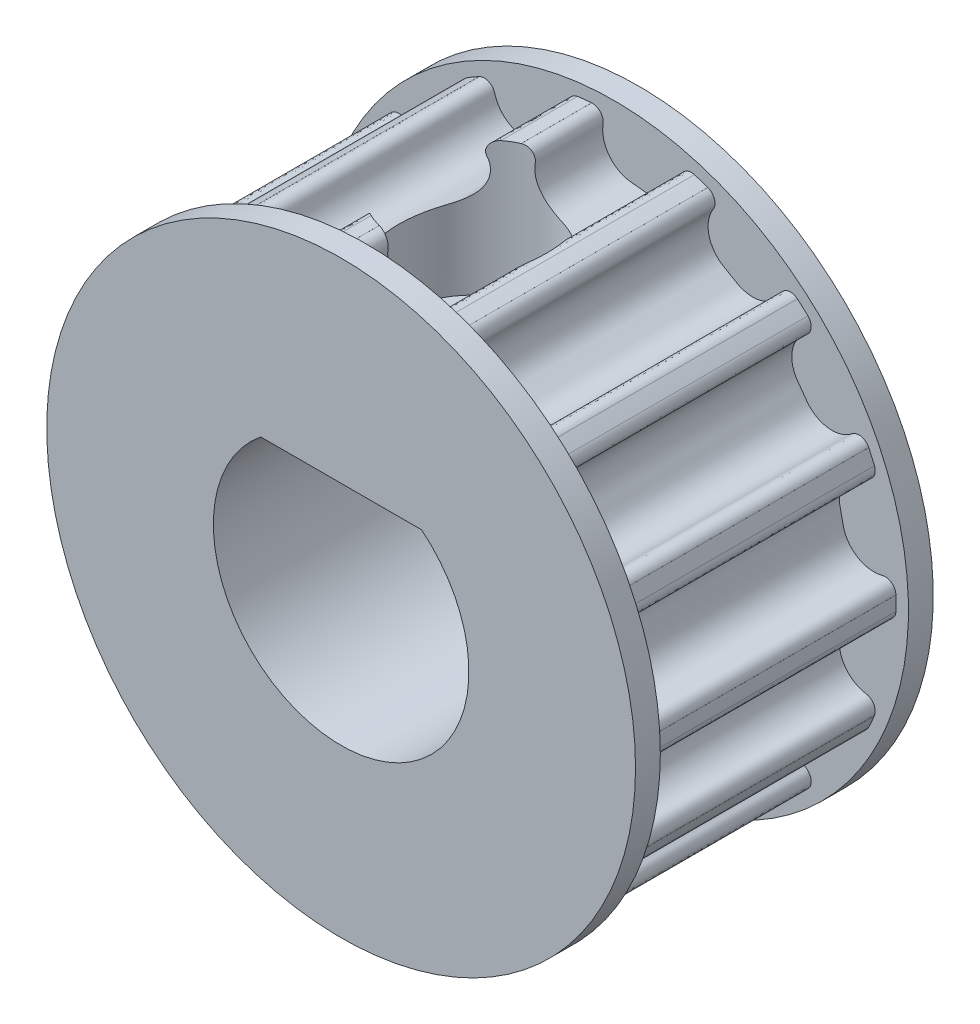
SolidWorks part; units mm, degrees
material "1060 合金"
ref_plane "前视基准面" through (0, 0, 0) normal (0, 0, 1) x (1, 0, 0)
ref_plane "上视基准面" through (0, 0, 0) normal (0, 1, 0) x (1, 0, 0)
ref_plane "右视基准面" through (0, 0, 0) normal (1, 0, 0) x (0, 0, -1)
sketch "草图1" plane through (0, 0, 0) normal (0, 0, 1) x (1, 0, 0)
  line L60 (11.3616, 0.2846) -> (11.36, 0.2846)
  line L61 (10.4936, 4.3606) -> (10.4951, 4.3611)
  line L62 (10.2635, 4.8812) -> (10.2622, 4.8805)
  line L63 (7.8128, 8.2517) -> (7.8139, 8.2528)
  line L64 (7.3909, 8.6337) -> (7.3899, 8.6326)
  line L65 (3.7811, 10.7161) -> (3.7817, 10.7175)
  line L66 (3.2402, 10.8934) -> (3.2398, 10.892)
  line L67 (-0.9044, 11.3275) -> (-0.9045, 11.3291)
  line L68 (-1.4707, 11.2696) -> (-1.4705, 11.268)
  line L69 (-5.4336, 9.9804) -> (-5.4342, 9.9817)
  line L70 (-5.9273, 9.6971) -> (-5.9265, 9.6958)
  line L71 (-9.0232, 6.9075) -> (-9.0243, 6.9085)
  line L72 (-9.359, 6.4479) -> (-9.3577, 6.447)
  line L73 (-11.0526, 2.6402) -> (-11.0541, 2.6407)
  line L74 (-11.1724, 2.0838) -> (-11.1709, 2.0835)
  line L75 (-11.1709, -2.0835) -> (-11.1725, -2.0837)
  line L76 (-11.0541, -2.6406) -> (-11.0526, -2.6402)
  line L77 (-9.3577, -6.447) -> (-9.359, -6.4478)
  line L78 (-9.0244, -6.9084) -> (-9.0232, -6.9075)
  line L79 (-5.9265, -9.6958) -> (-5.9273, -9.697)
  line L80 (-5.4343, -9.9817) -> (-5.4336, -9.9804)
  line L81 (-1.4705, -11.268) -> (-1.4707, -11.2696)
  line L82 (-0.9046, -11.3291) -> (-0.9044, -11.3275)
  line L83 (3.2398, -10.892) -> (3.2401, -10.8935)
  line L84 (3.7816, -10.7175) -> (3.7811, -10.7161)
  line L85 (7.3899, -8.6326) -> (7.3908, -8.6338)
  line L86 (7.8139, -8.2528) -> (7.8128, -8.2517)
  line L87 (10.2622, -4.8805) -> (10.2635, -4.8812)
  line L88 (10.4951, -4.3612) -> (10.4936, -4.3606)
  line L89 (11.36, -0.2846) -> (11.3615, -0.2847)
  arc A30 (11.3615, -0.2847) -> (11.3616, 0.2846) centre (0, 0) ccw
  arc A31 (10.4951, 4.3611) -> (10.2635, 4.8812) centre (0, 0) ccw
  arc A32 (7.8139, 8.2528) -> (7.3909, 8.6337) centre (0, 0) ccw
  arc A33 (3.7817, 10.7175) -> (3.2402, 10.8934) centre (0, 0) ccw
  arc A34 (-0.9045, 11.3291) -> (-1.4707, 11.2696) centre (0, 0) ccw
  arc A35 (-5.4342, 9.9817) -> (-5.9273, 9.6971) centre (0, 0) ccw
  arc A36 (-9.0243, 6.9085) -> (-9.359, 6.4479) centre (0, 0) ccw
  arc A37 (-11.0541, 2.6407) -> (-11.1724, 2.0838) centre (0, 0) ccw
  arc A38 (-11.1725, -2.0837) -> (-11.0541, -2.6406) centre (0, 0) ccw
  arc A39 (-9.359, -6.4478) -> (-9.0244, -6.9084) centre (0, 0) ccw
  arc A40 (-5.9273, -9.697) -> (-5.4343, -9.9817) centre (0, 0) ccw
  arc A41 (-1.4707, -11.2696) -> (-0.9046, -11.3291) centre (0, 0) ccw
  arc A42 (3.2401, -10.8935) -> (3.7816, -10.7175) centre (0, 0) ccw
  arc A43 (7.3908, -8.6338) -> (7.8139, -8.2528) centre (0, 0) ccw
  arc A44 (10.2635, -4.8812) -> (10.4951, -4.3612) centre (0, 0) ccw
  spline S30 degree 3 poles (11.36, 0.2846) (11.3594, 0.3098) (11.3551, 0.3475) (11.3399, 0.4088) (11.3213, 0.4559) (11.2906, 0.5111) (11.2605, 0.5518) (11.2165, 0.5972) (11.1768, 0.6286) (11.1226, 0.661) (11.0761, 0.681) (11.0275, 0.6948) (10.9903, 0.7018) (10.9526, 0.7056) (10.9147, 0.7061) (10.8769, 0.7034) (10.8159, 0.6926) (10.7357, 0.6738) (10.6343, 0.6561) (10.5355, 0.6475) (10.4032, 0.646) (10.2713, 0.6602) (10.1423, 0.6897) (10.0476, 0.7193) (9.9555, 0.7563) (9.8666, 0.8003) (9.7814, 0.8512) (9.7004, 0.9086) (9.6242, 0.9722) (9.5532, 1.0415) (9.4878, 1.1162) (9.4285, 1.1957) (9.3756, 1.2797) (9.3295, 1.3675) (9.2904, 1.4587) (9.2582, 1.5527) (9.2305, 1.6667) (9.2037, 1.7994) (9.1713, 1.9494) (9.1399, 2.0997) (9.1104, 2.2318) (9.0894, 2.3472) (9.0805, 2.4461) (9.0791, 2.5453) (9.0856, 2.6444) (9.0997, 2.7426) (9.1216, 2.8394) (9.1509, 2.9342) (9.1876, 3.0264) (9.2313, 3.1155) (9.2819, 3.2008) (9.3391, 3.2819) (9.4024, 3.3584) (9.4715, 3.4296) (9.546, 3.4952) (9.6518, 3.5746) (9.7665, 3.6412) (9.888, 3.6937) (9.9818, 3.726) (10.0816, 3.7511) (10.1625, 3.7665) (10.2226, 3.7815) (10.2582, 3.7944) (10.2927, 3.8102) (10.3256, 3.829) (10.367, 3.8578) (10.4045, 3.8919) (10.4453, 3.9401) (10.4726, 3.9828) (10.4994, 4.0399) (10.5147, 4.0882) (10.5257, 4.1504) (10.5285, 4.2136) (10.5186, 4.289) (10.5033, 4.3373) (10.4936, 4.3606) knots 0 0 0 0 0.011986 0.017979 0.029966 0.035959 0.047945 0.053938 0.065925 0.071918 0.083904 0.089897 0.09589 0.101884 0.107877 0.11387 0.119863 0.137299 0.153003 0.168706 0.18441 0.215817 0.23152 0.247224 0.262927 0.278631 0.294334 0.310038 0.325741 0.341445 0.357148 0.372852 0.388555 0.404259 0.419962 0.435666 0.451369 0.475685 0.5 0.524315 0.548631 0.564334 0.580038 0.595741 0.611445 0.627148 0.642852 0.658555 0.674259 0.689962 0.705666 0.721369 0.737073 0.752776 0.76848 0.784183 0.81559 0.831294 0.846997 0.862701 0.880137 0.88613 0.892123 0.898116 0.90411 0.910103 0.922089 0.928082 0.940068 0.946062 0.958048 0.964041 0.976027 0.988014 1 1 1 1
  spline S31 degree 3 poles (10.2622, 4.8805) (10.2513, 4.9033) (10.2321, 4.936) (10.1932, 4.9858) (10.1571, 5.0213) (10.1066, 5.0593) (10.0625, 5.0842) (10.0039, 5.1077) (9.9548, 5.1203) (9.8922, 5.1278) (9.8415, 5.1272) (9.7915, 5.12) (9.7546, 5.1113) (9.7187, 5.0994) (9.6839, 5.0844) (9.6504, 5.0666) (9.5991, 5.0319) (9.5335, 4.9821) (9.4481, 4.9248) (9.3613, 4.8766) (9.241, 4.8215) (9.1148, 4.7809) (8.9849, 4.7553) (8.8864, 4.7439) (8.7872, 4.7402) (8.688, 4.7442) (8.5895, 4.7561) (8.4922, 4.7756) (8.3967, 4.8026) (8.3037, 4.8371) (8.2136, 4.8787) (8.127, 4.9273) (8.0446, 4.9825) (7.9667, 5.0439) (7.8939, 5.1114) (7.8263, 5.1841) (7.7546, 5.277) (7.6762, 5.3873) (7.5855, 5.5112) (7.4957, 5.6357) (7.415, 5.7444) (7.3488, 5.8413) (7.3005, 5.928) (7.2589, 6.0181) (7.2245, 6.1112) (7.1975, 6.2067) (7.1781, 6.304) (7.1663, 6.4025) (7.1623, 6.5017) (7.1661, 6.6008) (7.1776, 6.6994) (7.1968, 6.7968) (7.2236, 6.8923) (7.2577, 6.9855) (7.2991, 7.0757) (7.3635, 7.1913) (7.4412, 7.2988) (7.5308, 7.3961) (7.6034, 7.4638) (7.6843, 7.5273) (7.7519, 7.5743) (7.8008, 7.6125) (7.8281, 7.6387) (7.8531, 7.6672) (7.8755, 7.6977) (7.9017, 7.7409) (7.922, 7.7873) (7.9396, 7.8479) (7.9472, 7.898) (7.9485, 7.9611) (7.9428, 8.0115) (7.9276, 8.0728) (7.9044, 8.1317) (7.8647, 8.1965) (7.8311, 8.2344) (7.8128, 8.2517) knots 0 0 0 0 0.011986 0.017979 0.029966 0.035959 0.047945 0.053938 0.065925 0.071918 0.083904 0.089897 0.09589 0.101884 0.107877 0.11387 0.119863 0.137299 0.153003 0.168706 0.18441 0.215817 0.23152 0.247224 0.262927 0.278631 0.294334 0.310038 0.325741 0.341445 0.357148 0.372852 0.388555 0.404259 0.419962 0.435666 0.451369 0.475685 0.5 0.524315 0.548631 0.564334 0.580038 0.595741 0.611445 0.627148 0.642852 0.658555 0.674259 0.689962 0.705666 0.721369 0.737073 0.752776 0.76848 0.784183 0.81559 0.831294 0.846997 0.862701 0.880137 0.88613 0.892123 0.898116 0.90411 0.910103 0.922089 0.928082 0.940068 0.946062 0.958048 0.964041 0.976027 0.988014 1 1 1 1
  spline S32 degree 3 poles (7.3899, 8.6326) (7.3707, 8.649) (7.3398, 8.6711) (7.284, 8.7007) (7.2366, 8.7184) (7.1751, 8.7326) (7.1246, 8.7374) (7.0615, 8.7351) (7.0116, 8.7266) (6.9513, 8.708) (6.9052, 8.6868) (6.8625, 8.6599) (6.8324, 8.637) (6.8043, 8.6115) (6.7786, 8.5836) (6.7554, 8.5537) (6.7225, 8.5012) (6.6829, 8.429) (6.6281, 8.3419) (6.5684, 8.2626) (6.481, 8.1633) (6.3822, 8.0748) (6.274, 7.9987) (6.1886, 7.9482) (6.0995, 7.9044) (6.0073, 7.8678) (5.9124, 7.8386) (5.8156, 7.8168) (5.7174, 7.8027) (5.6184, 7.7963) (5.5191, 7.7977) (5.4203, 7.8069) (5.3225, 7.8237) (5.2263, 7.8482) (5.1324, 7.8802) (5.0411, 7.9192) (4.9378, 7.9748) (4.8213, 8.0437) (4.6881, 8.12) (4.5554, 8.1972) (4.4375, 8.2637) (4.3376, 8.3253) (4.2582, 8.3849) (4.1836, 8.4502) (4.1143, 8.5213) (4.0508, 8.5976) (3.9934, 8.6786) (3.9426, 8.7638) (3.8986, 8.8527) (3.8617, 8.9449) (3.8322, 9.0396) (3.8101, 9.1363) (3.7957, 9.2345) (3.789, 9.3335) (3.7901, 9.4328) (3.8019, 9.5646) (3.8292, 9.6944) (3.8714, 9.8197) (3.9102, 9.9111) (3.9583, 10.002) (4.001, 10.0725) (4.0301, 10.1272) (4.0443, 10.1623) (4.0556, 10.1984) (4.0637, 10.2355) (4.07, 10.2856) (4.0698, 10.3362) (4.0612, 10.3988) (4.0478, 10.4476) (4.0232, 10.5058) (3.9976, 10.5495) (3.9588, 10.5993) (3.9136, 10.6437) (3.851, 10.6867) (3.8049, 10.7077) (3.7811, 10.7161) knots 0 0 0 0 0.011986 0.017979 0.029966 0.035959 0.047945 0.053938 0.065925 0.071918 0.083904 0.089897 0.09589 0.101884 0.107877 0.11387 0.119863 0.137299 0.153003 0.168706 0.18441 0.215817 0.23152 0.247224 0.262927 0.278631 0.294334 0.310038 0.325741 0.341445 0.357148 0.372852 0.388555 0.404259 0.419962 0.435666 0.451369 0.475685 0.5 0.524315 0.548631 0.564334 0.580038 0.595741 0.611445 0.627148 0.642852 0.658555 0.674259 0.689962 0.705666 0.721369 0.737073 0.752776 0.76848 0.784183 0.81559 0.831294 0.846997 0.862701 0.880137 0.88613 0.892123 0.898116 0.90411 0.910103 0.922089 0.928082 0.940068 0.946062 0.958048 0.964041 0.976027 0.988014 1 1 1 1
  spline S33 degree 3 poles (3.2398, 10.892) (3.2156, 10.8992) (3.1784, 10.9068) (3.1154, 10.9112) (3.0648, 10.9081) (3.0029, 10.896) (2.9549, 10.8799) (2.8982, 10.8521) (2.856, 10.824) (2.8084, 10.7825) (2.775, 10.7444) (2.7469, 10.7024) (2.7287, 10.6692) (2.7134, 10.6346) (2.7013, 10.5987) (2.6922, 10.5619) (2.6836, 10.5005) (2.6767, 10.4184) (2.6622, 10.3166) (2.6399, 10.2199) (2.6003, 10.0936) (2.5461, 9.9726) (2.4782, 9.859) (2.4207, 9.7781) (2.3571, 9.7019) (2.2878, 9.631) (2.2131, 9.5657) (2.1335, 9.5064) (2.0495, 9.4536) (1.9616, 9.4075) (1.8704, 9.3684) (1.7764, 9.3366) (1.6802, 9.3122) (1.5824, 9.2954) (1.4835, 9.2865) (1.3843, 9.2849) (1.2673, 9.2938) (1.1328, 9.3093) (0.9801, 9.3248) (0.8275, 9.3414) (0.6927, 9.3542) (0.5764, 9.3698) (0.4796, 9.392) (0.3849, 9.4213) (0.2927, 9.458) (0.2036, 9.5019) (0.1183, 9.5525) (0.0372, 9.6097) (-0.0392, 9.6731) (-0.1103, 9.7422) (-0.1759, 9.8168) (-0.2354, 9.8962) (-0.2885, 9.98) (-0.3349, 10.0677) (-0.3742, 10.1588) (-0.417, 10.284) (-0.4449, 10.4137) (-0.4573, 10.5454) (-0.459, 10.6447) (-0.4521, 10.7473) (-0.4418, 10.829) (-0.4374, 10.8908) (-0.4387, 10.9287) (-0.4431, 10.9663) (-0.4508, 11.0034) (-0.4654, 11.0518) (-0.4862, 11.0979) (-0.5195, 11.1516) (-0.5516, 11.1908) (-0.5977, 11.2339) (-0.6389, 11.2634) (-0.6946, 11.2931) (-0.7539, 11.3153) (-0.8286, 11.3291) (-0.8793, 11.3296) (-0.9044, 11.3275) knots 0 0 0 0 0.011986 0.017979 0.029966 0.035959 0.047945 0.053938 0.065925 0.071918 0.083904 0.089897 0.09589 0.101884 0.107877 0.11387 0.119863 0.137299 0.153003 0.168706 0.18441 0.215817 0.23152 0.247224 0.262927 0.278631 0.294334 0.310038 0.325741 0.341445 0.357148 0.372852 0.388555 0.404259 0.419962 0.435666 0.451369 0.475685 0.5 0.524315 0.548631 0.564334 0.580038 0.595741 0.611445 0.627148 0.642852 0.658555 0.674259 0.689962 0.705666 0.721369 0.737073 0.752776 0.76848 0.784183 0.81559 0.831294 0.846997 0.862701 0.880137 0.88613 0.892123 0.898116 0.90411 0.910103 0.922089 0.928082 0.940068 0.946062 0.958048 0.964041 0.976027 0.988014 1 1 1 1
  spline S34 degree 3 poles (-1.4705, 11.268) (-1.4955, 11.2648) (-1.5326, 11.2566) (-1.5919, 11.235) (-1.6368, 11.2116) (-1.6885, 11.1754) (-1.7258, 11.1411) (-1.7663, 11.0927) (-1.7935, 11.0499) (-1.82, 10.9926) (-1.8351, 10.9442) (-1.8436, 10.8944) (-1.8468, 10.8567) (-1.8466, 10.8188) (-1.8431, 10.7811) (-1.8364, 10.7438) (-1.8193, 10.6842) (-1.7922, 10.6065) (-1.7641, 10.5075) (-1.7452, 10.4101) (-1.7299, 10.2786) (-1.7303, 10.146) (-1.7461, 10.0147) (-1.7657, 9.9174) (-1.7928, 9.8219) (-1.8273, 9.7289) (-1.869, 9.6388) (-1.9176, 9.5523) (-1.9728, 9.4699) (-2.0344, 9.392) (-2.1018, 9.3192) (-2.1747, 9.2519) (-2.2527, 9.1905) (-2.3352, 9.1354) (-2.4219, 9.087) (-2.5119, 9.0452) (-2.6224, 9.0057) (-2.7516, 8.9652) (-2.8974, 8.9173) (-3.0436, 8.8704) (-3.1719, 8.8272) (-3.2845, 8.7942) (-3.3819, 8.7751) (-3.4804, 8.7633) (-3.5796, 8.7594) (-3.6787, 8.7632) (-3.7773, 8.7748) (-3.8746, 8.7941) (-3.9702, 8.8209) (-4.0633, 8.8551) (-4.1535, 8.8965) (-4.2402, 8.9449) (-4.3228, 8.9999) (-4.4008, 9.0612) (-4.4738, 9.1284) (-4.5639, 9.2253) (-4.6421, 9.3324) (-4.707, 9.4477) (-4.7489, 9.5377) (-4.7844, 9.6343) (-4.8082, 9.7131) (-4.8293, 9.7713) (-4.8459, 9.8054) (-4.8652, 9.838) (-4.8873, 9.8687) (-4.9203, 9.907) (-4.9581, 9.9407) (-5.0104, 9.9762) (-5.0556, 9.9989) (-5.1153, 10.0196) (-5.1649, 10.0298) (-5.2279, 10.0342) (-5.2911, 10.0304) (-5.365, 10.0127) (-5.4114, 9.9924) (-5.4336, 9.9804) knots 0 0 0 0 0.011986 0.017979 0.029966 0.035959 0.047945 0.053938 0.065925 0.071918 0.083904 0.089897 0.09589 0.101884 0.107877 0.11387 0.119863 0.137299 0.153003 0.168706 0.18441 0.215817 0.23152 0.247224 0.262927 0.278631 0.294334 0.310038 0.325741 0.341445 0.357148 0.372852 0.388555 0.404259 0.419962 0.435666 0.451369 0.475685 0.5 0.524315 0.548631 0.564334 0.580038 0.595741 0.611445 0.627148 0.642852 0.658555 0.674259 0.689962 0.705666 0.721369 0.737073 0.752776 0.76848 0.784183 0.81559 0.831294 0.846997 0.862701 0.880137 0.88613 0.892123 0.898116 0.90411 0.910103 0.922089 0.928082 0.940068 0.946062 0.958048 0.964041 0.976027 0.988014 1 1 1 1
  spline S35 degree 3 poles (-5.9265, 9.6958) (-5.948, 9.6826) (-5.9785, 9.6601) (-6.024, 9.6162) (-6.0555, 9.5766) (-6.088, 9.5224) (-6.1081, 9.4759) (-6.1254, 9.4152) (-6.1328, 9.3651) (-6.1337, 9.302) (-6.1278, 9.2517) (-6.1154, 9.2027) (-6.1029, 9.1669) (-6.0874, 9.1324) (-6.0688, 9.0994) (-6.0476, 9.068) (-6.0077, 9.0205) (-5.9513, 8.9605) (-5.8854, 8.8815) (-5.8284, 8.8002) (-5.7611, 8.6864) (-5.7074, 8.5651) (-5.6685, 8.4386) (-5.6468, 8.3418) (-5.6327, 8.2436) (-5.6264, 8.1445) (-5.6279, 8.0453) (-5.6371, 7.9465) (-5.654, 7.8487) (-5.6786, 7.7526) (-5.7105, 7.6586) (-5.7498, 7.5675) (-5.7961, 7.4797) (-5.8491, 7.3958) (-5.9085, 7.3163) (-5.9738, 7.2415) (-6.0586, 7.1605) (-6.1602, 7.071) (-6.2739, 6.9679) (-6.3883, 6.8655) (-6.488, 6.7739) (-6.5774, 6.698) (-6.6587, 6.6409) (-6.7439, 6.5901) (-6.8329, 6.5462) (-6.925, 6.5093) (-7.0198, 6.4798) (-7.1165, 6.4578) (-7.2147, 6.4435) (-7.3137, 6.4368) (-7.413, 6.438) (-7.5118, 6.4469) (-7.6096, 6.4636) (-7.7059, 6.4878) (-7.7999, 6.5195) (-7.9216, 6.5715) (-8.0366, 6.6375) (-8.1428, 6.7164) (-8.2177, 6.7815) (-8.2893, 6.8554) (-8.3431, 6.9177) (-8.3862, 6.9623) (-8.4151, 6.9867) (-8.446, 7.0086) (-8.4788, 7.0277) (-8.5245, 7.0492) (-8.5727, 7.0646) (-8.6349, 7.0758) (-8.6855, 7.0781) (-8.7484, 7.0728) (-8.7978, 7.0619) (-8.8572, 7.0404) (-8.9134, 7.0112) (-8.9737, 6.9649) (-9.0079, 6.9275) (-9.0232, 6.9075) knots 0 0 0 0 0.011986 0.017979 0.029966 0.035959 0.047945 0.053938 0.065925 0.071918 0.083904 0.089897 0.09589 0.101884 0.107877 0.11387 0.119863 0.137299 0.153003 0.168706 0.18441 0.215817 0.23152 0.247224 0.262927 0.278631 0.294334 0.310038 0.325741 0.341445 0.357148 0.372852 0.388555 0.404259 0.419962 0.435666 0.451369 0.475685 0.5 0.524315 0.548631 0.564334 0.580038 0.595741 0.611445 0.627148 0.642852 0.658555 0.674259 0.689962 0.705666 0.721369 0.737073 0.752776 0.76848 0.784183 0.81559 0.831294 0.846997 0.862701 0.880137 0.88613 0.892123 0.898116 0.90411 0.910103 0.922089 0.928082 0.940068 0.946062 0.958048 0.964041 0.976027 0.988014 1 1 1 1
  spline S36 degree 3 poles (-9.3577, 6.447) (-9.372, 6.4263) (-9.3908, 6.3932) (-9.4144, 6.3347) (-9.4271, 6.2856) (-9.4348, 6.223) (-9.4343, 6.1723) (-9.4254, 6.1098) (-9.4117, 6.061) (-9.3869, 6.003) (-9.361, 5.9594) (-9.3298, 5.9197) (-9.3038, 5.8921) (-9.2756, 5.8669) (-9.2452, 5.8443) (-9.213, 5.8242) (-9.1573, 5.7971) (-9.0814, 5.7652) (-8.989, 5.7199) (-8.9039, 5.6688) (-8.7961, 5.5922) (-8.6977, 5.5032) (-8.6107, 5.4035) (-8.5515, 5.3239) (-8.4987, 5.2398) (-8.4527, 5.1519) (-8.4136, 5.0607) (-8.3819, 4.9667) (-8.3576, 4.8705) (-8.3409, 4.7726) (-8.3319, 4.6738) (-8.3307, 4.5746) (-8.3372, 4.4756) (-8.3515, 4.3774) (-8.3735, 4.2806) (-8.4027, 4.1857) (-8.4473, 4.0772) (-8.5036, 3.9541) (-8.5656, 3.8136) (-8.6285, 3.6736) (-8.6823, 3.5494) (-8.7331, 3.4436) (-8.7841, 3.3584) (-8.8413, 3.2774) (-8.9047, 3.201) (-8.9739, 3.1299) (-9.0484, 3.0644) (-9.1279, 3.005) (-9.2118, 2.9519) (-9.2995, 2.9056) (-9.3906, 2.8663) (-9.4846, 2.8342) (-9.5807, 2.8096) (-9.6785, 2.7926) (-9.7773, 2.7834) (-9.9096, 2.7813) (-10.0415, 2.7949) (-10.1706, 2.8238) (-10.2655, 2.8528) (-10.361, 2.8911) (-10.4355, 2.9262) (-10.493, 2.9494) (-10.5294, 2.9599) (-10.5665, 2.9674) (-10.6042, 2.9715) (-10.6547, 2.9726) (-10.705, 2.967) (-10.7663, 2.952) (-10.8135, 2.9335) (-10.8688, 2.903) (-10.9096, 2.8729) (-10.955, 2.8291) (-10.9945, 2.7796) (-11.0307, 2.7128) (-11.0468, 2.6648) (-11.0526, 2.6402) knots 0 0 0 0 0.011986 0.017979 0.029966 0.035959 0.047945 0.053938 0.065925 0.071918 0.083904 0.089897 0.09589 0.101884 0.107877 0.11387 0.119863 0.137299 0.153003 0.168706 0.18441 0.215817 0.23152 0.247224 0.262927 0.278631 0.294334 0.310038 0.325741 0.341445 0.357148 0.372852 0.388555 0.404259 0.419962 0.435666 0.451369 0.475685 0.5 0.524315 0.548631 0.564334 0.580038 0.595741 0.611445 0.627148 0.642852 0.658555 0.674259 0.689962 0.705666 0.721369 0.737073 0.752776 0.76848 0.784183 0.81559 0.831294 0.846997 0.862701 0.880137 0.88613 0.892123 0.898116 0.90411 0.910103 0.922089 0.928082 0.940068 0.946062 0.958048 0.964041 0.976027 0.988014 1 1 1 1
  spline S37 degree 3 poles (-11.1709, 2.0835) (-11.1756, 2.0587) (-11.1792, 2.0209) (-11.1771, 1.9578) (-11.1687, 1.9079) (-11.1502, 1.8475) (-11.1291, 1.8014) (-11.0956, 1.7479) (-11.0633, 1.7089) (-11.017, 1.666) (-10.9756, 1.6367) (-10.9309, 1.6132) (-10.896, 1.5985) (-10.8599, 1.587) (-10.823, 1.5786) (-10.7854, 1.5734) (-10.7235, 1.5713) (-10.6412, 1.573) (-10.5384, 1.5692) (-10.4399, 1.5571) (-10.3101, 1.531) (-10.1841, 1.4897) (-10.0641, 1.434) (-9.9776, 1.3854) (-9.8952, 1.3301) (-9.8174, 1.2685) (-9.7446, 1.201) (-9.6773, 1.1281) (-9.616, 1.0501) (-9.561, 0.9675) (-9.5126, 0.8809) (-9.4711, 0.7907) (-9.4368, 0.6976) (-9.4099, 0.602) (-9.3907, 0.5047) (-9.3788, 0.4062) (-9.3753, 0.2889) (-9.3767, 0.1535) (-9.3762, 0) (-9.3767, -0.1535) (-9.3753, -0.2889) (-9.3788, -0.4062) (-9.3907, -0.5047) (-9.4099, -0.602) (-9.4368, -0.6976) (-9.4711, -0.7907) (-9.5126, -0.8809) (-9.561, -0.9675) (-9.616, -1.0501) (-9.6773, -1.1281) (-9.7446, -1.201) (-9.8174, -1.2685) (-9.8952, -1.3301) (-9.9776, -1.3854) (-10.0641, -1.434) (-10.1841, -1.4897) (-10.3101, -1.531) (-10.4399, -1.5571) (-10.5384, -1.5692) (-10.6412, -1.573) (-10.7235, -1.5713) (-10.7854, -1.5734) (-10.823, -1.5786) (-10.8599, -1.587) (-10.896, -1.5985) (-10.9426, -1.6181) (-10.9863, -1.6436) (-11.0362, -1.6823) (-11.0718, -1.7184) (-11.1099, -1.7687) (-11.1349, -1.8127) (-11.1586, -1.8713) (-11.1745, -1.9326) (-11.1805, -2.0083) (-11.1756, -2.0587) (-11.1709, -2.0835) knots 0 0 0 0 0.011986 0.017979 0.029966 0.035959 0.047945 0.053938 0.065925 0.071918 0.083904 0.089897 0.09589 0.101884 0.107877 0.11387 0.119863 0.137299 0.153003 0.168706 0.18441 0.215817 0.23152 0.247224 0.262927 0.278631 0.294334 0.310038 0.325741 0.341445 0.357148 0.372852 0.388555 0.404259 0.419962 0.435666 0.451369 0.475685 0.5 0.524315 0.548631 0.564334 0.580038 0.595741 0.611445 0.627148 0.642852 0.658555 0.674259 0.689962 0.705666 0.721369 0.737073 0.752776 0.76848 0.784183 0.81559 0.831294 0.846997 0.862701 0.880137 0.88613 0.892123 0.898116 0.90411 0.910103 0.922089 0.928082 0.940068 0.946062 0.958048 0.964041 0.976027 0.988014 1 1 1 1
  spline S38 degree 3 poles (-11.0526, -2.6402) (-11.0468, -2.6648) (-11.0347, -2.7008) (-11.0071, -2.7576) (-10.9791, -2.7998) (-10.9376, -2.8474) (-10.8997, -2.8809) (-10.8473, -2.9162) (-10.8019, -2.9387) (-10.7421, -2.959) (-10.6924, -2.969) (-10.642, -2.9723) (-10.6042, -2.9715) (-10.5665, -2.9674) (-10.5294, -2.9599) (-10.493, -2.9494) (-10.4355, -2.9262) (-10.361, -2.8911) (-10.2655, -2.8528) (-10.1706, -2.8238) (-10.0415, -2.7949) (-9.9096, -2.7813) (-9.7773, -2.7834) (-9.6785, -2.7926) (-9.5807, -2.8096) (-9.4846, -2.8342) (-9.3906, -2.8663) (-9.2995, -2.9056) (-9.2118, -2.9519) (-9.1279, -3.005) (-9.0484, -3.0644) (-8.9739, -3.1299) (-8.9047, -3.201) (-8.8413, -3.2774) (-8.7841, -3.3584) (-8.7331, -3.4436) (-8.6823, -3.5494) (-8.6285, -3.6736) (-8.5656, -3.8136) (-8.5036, -3.9541) (-8.4473, -4.0772) (-8.4027, -4.1857) (-8.3735, -4.2806) (-8.3515, -4.3774) (-8.3372, -4.4756) (-8.3307, -4.5746) (-8.3319, -4.6738) (-8.3409, -4.7726) (-8.3576, -4.8705) (-8.3819, -4.9667) (-8.4136, -5.0607) (-8.4527, -5.1519) (-8.4987, -5.2398) (-8.5515, -5.3239) (-8.6107, -5.4035) (-8.6977, -5.5032) (-8.7961, -5.5922) (-8.9039, -5.6688) (-8.989, -5.7199) (-9.0814, -5.7652) (-9.1573, -5.7971) (-9.213, -5.8242) (-9.2452, -5.8443) (-9.2756, -5.8669) (-9.3038, -5.8921) (-9.3384, -5.9289) (-9.368, -5.97) (-9.3978, -6.0257) (-9.4157, -6.0731) (-9.43, -6.1346) (-9.4349, -6.185) (-9.4328, -6.2481) (-9.4224, -6.3106) (-9.397, -6.3822) (-9.372, -6.4263) (-9.3577, -6.447) knots 0 0 0 0 0.011986 0.017979 0.029966 0.035959 0.047945 0.053938 0.065925 0.071918 0.083904 0.089897 0.09589 0.101884 0.107877 0.11387 0.119863 0.137299 0.153003 0.168706 0.18441 0.215817 0.23152 0.247224 0.262927 0.278631 0.294334 0.310038 0.325741 0.341445 0.357148 0.372852 0.388555 0.404259 0.419962 0.435666 0.451369 0.475685 0.5 0.524315 0.548631 0.564334 0.580038 0.595741 0.611445 0.627148 0.642852 0.658555 0.674259 0.689962 0.705666 0.721369 0.737073 0.752776 0.76848 0.784183 0.81559 0.831294 0.846997 0.862701 0.880137 0.88613 0.892123 0.898116 0.90411 0.910103 0.922089 0.928082 0.940068 0.946062 0.958048 0.964041 0.976027 0.988014 1 1 1 1
  spline S39 degree 3 poles (-9.0232, -6.9075) (-9.0079, -6.9275) (-8.9822, -6.9555) (-8.9338, -6.9961) (-8.8911, -7.0233) (-8.8339, -7.05) (-8.7855, -7.0652) (-8.7234, -7.076) (-8.6727, -7.0781) (-8.6099, -7.0724) (-8.5604, -7.0613) (-8.513, -7.0439) (-8.4788, -7.0277) (-8.446, -7.0086) (-8.4151, -6.9867) (-8.3862, -6.9623) (-8.3431, -6.9177) (-8.2893, -6.8554) (-8.2177, -6.7815) (-8.1428, -6.7164) (-8.0366, -6.6375) (-7.9216, -6.5715) (-7.7999, -6.5195) (-7.7059, -6.4878) (-7.6096, -6.4636) (-7.5118, -6.4469) (-7.413, -6.438) (-7.3137, -6.4368) (-7.2147, -6.4435) (-7.1165, -6.4578) (-7.0198, -6.4798) (-6.925, -6.5093) (-6.8329, -6.5462) (-6.7439, -6.5901) (-6.6587, -6.6409) (-6.5774, -6.698) (-6.488, -6.7739) (-6.3883, -6.8655) (-6.2739, -6.9679) (-6.1602, -7.071) (-6.0586, -7.1605) (-5.9738, -7.2415) (-5.9085, -7.3163) (-5.8491, -7.3958) (-5.7961, -7.4797) (-5.7498, -7.5675) (-5.7105, -7.6586) (-5.6786, -7.7526) (-5.654, -7.8487) (-5.6371, -7.9465) (-5.6279, -8.0453) (-5.6264, -8.1445) (-5.6327, -8.2436) (-5.6468, -8.3418) (-5.6685, -8.4386) (-5.7074, -8.5651) (-5.7611, -8.6864) (-5.8284, -8.8002) (-5.8854, -8.8815) (-5.9513, -8.9605) (-6.0077, -9.0205) (-6.0476, -9.068) (-6.0688, -9.0994) (-6.0874, -9.1324) (-6.1029, -9.1669) (-6.1196, -9.2146) (-6.1298, -9.2642) (-6.1344, -9.3272) (-6.1315, -9.3778) (-6.1196, -9.4398) (-6.1036, -9.4878) (-6.076, -9.5446) (-6.041, -9.5974) (-5.9887, -9.6525) (-5.948, -9.6826) (-5.9265, -9.6958) knots 0 0 0 0 0.011986 0.017979 0.029966 0.035959 0.047945 0.053938 0.065925 0.071918 0.083904 0.089897 0.09589 0.101884 0.107877 0.11387 0.119863 0.137299 0.153003 0.168706 0.18441 0.215817 0.23152 0.247224 0.262927 0.278631 0.294334 0.310038 0.325741 0.341445 0.357148 0.372852 0.388555 0.404259 0.419962 0.435666 0.451369 0.475685 0.5 0.524315 0.548631 0.564334 0.580038 0.595741 0.611445 0.627148 0.642852 0.658555 0.674259 0.689962 0.705666 0.721369 0.737073 0.752776 0.76848 0.784183 0.81559 0.831294 0.846997 0.862701 0.880137 0.88613 0.892123 0.898116 0.90411 0.910103 0.922089 0.928082 0.940068 0.946062 0.958048 0.964041 0.976027 0.988014 1 1 1 1
  spline S40 degree 3 poles (-5.4336, -9.9804) (-5.4114, -9.9924) (-5.3766, -10.0076) (-5.3159, -10.025) (-5.2658, -10.0325) (-5.2027, -10.0335) (-5.1523, -10.0278) (-5.0911, -10.0124) (-5.044, -9.9937) (-4.9889, -9.9629) (-4.9483, -9.9327) (-4.9121, -9.8974) (-4.8873, -9.8687) (-4.8652, -9.838) (-4.8459, -9.8054) (-4.8293, -9.7713) (-4.8082, -9.7131) (-4.7844, -9.6343) (-4.7489, -9.5377) (-4.707, -9.4477) (-4.6421, -9.3324) (-4.5639, -9.2253) (-4.4738, -9.1284) (-4.4008, -9.0612) (-4.3228, -8.9999) (-4.2402, -8.9449) (-4.1535, -8.8965) (-4.0633, -8.8551) (-3.9702, -8.8209) (-3.8746, -8.7941) (-3.7773, -8.7748) (-3.6787, -8.7632) (-3.5796, -8.7594) (-3.4804, -8.7633) (-3.3819, -8.7751) (-3.2845, -8.7942) (-3.1719, -8.8272) (-3.0436, -8.8704) (-2.8974, -8.9173) (-2.7516, -8.9652) (-2.6224, -9.0057) (-2.5119, -9.0452) (-2.4219, -9.087) (-2.3352, -9.1354) (-2.2527, -9.1905) (-2.1747, -9.2519) (-2.1018, -9.3192) (-2.0344, -9.392) (-1.9728, -9.4699) (-1.9176, -9.5523) (-1.869, -9.6388) (-1.8273, -9.7289) (-1.7928, -9.8219) (-1.7657, -9.9174) (-1.7461, -10.0147) (-1.7303, -10.146) (-1.7299, -10.2786) (-1.7452, -10.4101) (-1.7641, -10.5075) (-1.7922, -10.6065) (-1.8193, -10.6842) (-1.8364, -10.7438) (-1.8431, -10.7811) (-1.8466, -10.8188) (-1.8468, -10.8567) (-1.8426, -10.907) (-1.8318, -10.9565) (-1.8104, -11.0159) (-1.7871, -11.0609) (-1.751, -11.1127) (-1.7169, -11.1501) (-1.6685, -11.1907) (-1.6151, -11.2248) (-1.5449, -11.2539) (-1.4955, -11.2648) (-1.4705, -11.268) knots 0 0 0 0 0.011986 0.017979 0.029966 0.035959 0.047945 0.053938 0.065925 0.071918 0.083904 0.089897 0.09589 0.101884 0.107877 0.11387 0.119863 0.137299 0.153003 0.168706 0.18441 0.215817 0.23152 0.247224 0.262927 0.278631 0.294334 0.310038 0.325741 0.341445 0.357148 0.372852 0.388555 0.404259 0.419962 0.435666 0.451369 0.475685 0.5 0.524315 0.548631 0.564334 0.580038 0.595741 0.611445 0.627148 0.642852 0.658555 0.674259 0.689962 0.705666 0.721369 0.737073 0.752776 0.76848 0.784183 0.81559 0.831294 0.846997 0.862701 0.880137 0.88613 0.892123 0.898116 0.90411 0.910103 0.922089 0.928082 0.940068 0.946062 0.958048 0.964041 0.976027 0.988014 1 1 1 1
  spline S41 degree 3 poles (-0.9044, -11.3275) (-0.8793, -11.3296) (-0.8413, -11.3292) (-0.7788, -11.3205) (-0.73, -11.3069) (-0.6719, -11.2822) (-0.6282, -11.2565) (-0.5786, -11.2175) (-0.5431, -11.1813) (-0.5053, -11.1308) (-0.4805, -11.0866) (-0.4617, -11.0397) (-0.4508, -11.0034) (-0.4431, -10.9663) (-0.4387, -10.9287) (-0.4374, -10.8908) (-0.4418, -10.829) (-0.4521, -10.7473) (-0.459, -10.6447) (-0.4573, -10.5454) (-0.4449, -10.4137) (-0.417, -10.284) (-0.3742, -10.1588) (-0.3349, -10.0677) (-0.2885, -9.98) (-0.2354, -9.8962) (-0.1759, -9.8168) (-0.1103, -9.7422) (-0.0392, -9.6731) (0.0372, -9.6097) (0.1183, -9.5525) (0.2036, -9.5019) (0.2927, -9.458) (0.3849, -9.4213) (0.4796, -9.392) (0.5764, -9.3698) (0.6927, -9.3542) (0.8275, -9.3414) (0.9801, -9.3248) (1.1328, -9.3093) (1.2673, -9.2938) (1.3843, -9.2849) (1.4835, -9.2865) (1.5824, -9.2954) (1.6802, -9.3122) (1.7764, -9.3366) (1.8704, -9.3684) (1.9616, -9.4075) (2.0495, -9.4536) (2.1335, -9.5064) (2.2131, -9.5657) (2.2878, -9.631) (2.3571, -9.7019) (2.4207, -9.7781) (2.4782, -9.859) (2.5461, -9.9726) (2.6003, -10.0936) (2.6399, -10.2199) (2.6622, -10.3166) (2.6767, -10.4184) (2.6836, -10.5005) (2.6922, -10.5619) (2.7013, -10.5987) (2.7134, -10.6346) (2.7287, -10.6692) (2.753, -10.7135) (2.783, -10.7543) (2.8267, -10.7999) (2.8663, -10.8315) (2.9203, -10.8642) (2.9667, -10.8844) (3.0274, -10.9019) (3.09, -10.9113) (3.166, -10.9093) (3.2156, -10.8992) (3.2398, -10.892) knots 0 0 0 0 0.011986 0.017979 0.029966 0.035959 0.047945 0.053938 0.065925 0.071918 0.083904 0.089897 0.09589 0.101884 0.107877 0.11387 0.119863 0.137299 0.153003 0.168706 0.18441 0.215817 0.23152 0.247224 0.262927 0.278631 0.294334 0.310038 0.325741 0.341445 0.357148 0.372852 0.388555 0.404259 0.419962 0.435666 0.451369 0.475685 0.5 0.524315 0.548631 0.564334 0.580038 0.595741 0.611445 0.627148 0.642852 0.658555 0.674259 0.689962 0.705666 0.721369 0.737073 0.752776 0.76848 0.784183 0.81559 0.831294 0.846997 0.862701 0.880137 0.88613 0.892123 0.898116 0.90411 0.910103 0.922089 0.928082 0.940068 0.946062 0.958048 0.964041 0.976027 0.988014 1 1 1 1
  spline S42 degree 3 poles (3.7811, -10.7161) (3.8049, -10.7077) (3.8395, -10.692) (3.893, -10.6585) (3.9321, -10.6263) (3.9751, -10.5801) (4.0045, -10.5388) (4.034, -10.483) (4.0517, -10.4355) (4.0657, -10.374) (4.0704, -10.3235) (4.0684, -10.2731) (4.0637, -10.2355) (4.0556, -10.1984) (4.0443, -10.1623) (4.0301, -10.1272) (4.001, -10.0725) (3.9583, -10.002) (3.9102, -9.9111) (3.8714, -9.8197) (3.8292, -9.6944) (3.8019, -9.5646) (3.7901, -9.4328) (3.789, -9.3335) (3.7957, -9.2345) (3.8101, -9.1363) (3.8322, -9.0396) (3.8617, -8.9449) (3.8986, -8.8527) (3.9426, -8.7638) (3.9934, -8.6786) (4.0508, -8.5976) (4.1143, -8.5213) (4.1836, -8.4502) (4.2582, -8.3849) (4.3376, -8.3253) (4.4375, -8.2637) (4.5554, -8.1972) (4.6881, -8.12) (4.8213, -8.0437) (4.9378, -7.9748) (5.0411, -7.9192) (5.1324, -7.8802) (5.2263, -7.8482) (5.3225, -7.8237) (5.4203, -7.8069) (5.5191, -7.7977) (5.6184, -7.7963) (5.7174, -7.8027) (5.8156, -7.8168) (5.9124, -7.8386) (6.0073, -7.8678) (6.0995, -7.9044) (6.1886, -7.9482) (6.274, -7.9987) (6.3822, -8.0748) (6.481, -8.1633) (6.5684, -8.2626) (6.6281, -8.3419) (6.6829, -8.429) (6.7225, -8.5012) (6.7554, -8.5537) (6.7786, -8.5836) (6.8043, -8.6115) (6.8324, -8.637) (6.8726, -8.6675) (6.9166, -8.6926) (6.975, -8.7165) (7.024, -8.7293) (7.0867, -8.7371) (7.1373, -8.7367) (7.1999, -8.728) (7.2609, -8.7111) (7.3295, -8.6784) (7.3707, -8.649) (7.3899, -8.6326) knots 0 0 0 0 0.011986 0.017979 0.029966 0.035959 0.047945 0.053938 0.065925 0.071918 0.083904 0.089897 0.09589 0.101884 0.107877 0.11387 0.119863 0.137299 0.153003 0.168706 0.18441 0.215817 0.23152 0.247224 0.262927 0.278631 0.294334 0.310038 0.325741 0.341445 0.357148 0.372852 0.388555 0.404259 0.419962 0.435666 0.451369 0.475685 0.5 0.524315 0.548631 0.564334 0.580038 0.595741 0.611445 0.627148 0.642852 0.658555 0.674259 0.689962 0.705666 0.721369 0.737073 0.752776 0.76848 0.784183 0.81559 0.831294 0.846997 0.862701 0.880137 0.88613 0.892123 0.898116 0.90411 0.910103 0.922089 0.928082 0.940068 0.946062 0.958048 0.964041 0.976027 0.988014 1 1 1 1
  spline S43 degree 3 poles (7.8128, -8.2517) (7.8311, -8.2344) (7.8563, -8.2059) (7.8917, -8.1536) (7.9143, -8.1083) (7.9348, -8.0486) (7.9448, -7.9989) (7.9491, -7.9359) (7.9459, -7.8854) (7.9337, -7.8234) (7.9174, -7.7754) (7.8951, -7.7301) (7.8755, -7.6977) (7.8531, -7.6672) (7.8281, -7.6387) (7.8008, -7.6125) (7.7519, -7.5743) (7.6843, -7.5273) (7.6034, -7.4638) (7.5308, -7.3961) (7.4412, -7.2988) (7.3635, -7.1913) (7.2991, -7.0757) (7.2577, -6.9855) (7.2236, -6.8923) (7.1968, -6.7968) (7.1776, -6.6994) (7.1661, -6.6008) (7.1623, -6.5017) (7.1663, -6.4025) (7.1781, -6.304) (7.1975, -6.2067) (7.2245, -6.1112) (7.2589, -6.0181) (7.3005, -5.928) (7.3488, -5.8413) (7.415, -5.7444) (7.4957, -5.6357) (7.5855, -5.5112) (7.6762, -5.3873) (7.7546, -5.277) (7.8263, -5.1841) (7.8939, -5.1114) (7.9667, -5.0439) (8.0446, -4.9825) (8.127, -4.9273) (8.2136, -4.8787) (8.3037, -4.8371) (8.3967, -4.8026) (8.4922, -4.7756) (8.5895, -4.7561) (8.688, -4.7442) (8.7872, -4.7402) (8.8864, -4.7439) (8.9849, -4.7553) (9.1148, -4.7809) (9.241, -4.8215) (9.3613, -4.8766) (9.4481, -4.9248) (9.5335, -4.9821) (9.5991, -5.0319) (9.6504, -5.0666) (9.6839, -5.0844) (9.7187, -5.0994) (9.7546, -5.1113) (9.8038, -5.1229) (9.8542, -5.1279) (9.9173, -5.1259) (9.9673, -5.1177) (10.0277, -5.0993) (10.0738, -5.0784) (10.1274, -5.045) (10.1763, -5.0047) (10.2256, -4.947) (10.2513, -4.9033) (10.2622, -4.8805) knots 0 0 0 0 0.011986 0.017979 0.029966 0.035959 0.047945 0.053938 0.065925 0.071918 0.083904 0.089897 0.09589 0.101884 0.107877 0.11387 0.119863 0.137299 0.153003 0.168706 0.18441 0.215817 0.23152 0.247224 0.262927 0.278631 0.294334 0.310038 0.325741 0.341445 0.357148 0.372852 0.388555 0.404259 0.419962 0.435666 0.451369 0.475685 0.5 0.524315 0.548631 0.564334 0.580038 0.595741 0.611445 0.627148 0.642852 0.658555 0.674259 0.689962 0.705666 0.721369 0.737073 0.752776 0.76848 0.784183 0.81559 0.831294 0.846997 0.862701 0.880137 0.88613 0.892123 0.898116 0.90411 0.910103 0.922089 0.928082 0.940068 0.946062 0.958048 0.964041 0.976027 0.988014 1 1 1 1
  spline S44 degree 3 poles (10.4936, -4.3606) (10.5033, -4.3373) (10.5148, -4.301) (10.5258, -4.2389) (10.528, -4.1883) (10.5224, -4.1254) (10.5114, -4.0759) (10.4897, -4.0166) (10.4662, -3.9718) (10.4298, -3.9201) (10.3955, -3.8829) (10.3567, -3.8506) (10.3256, -3.829) (10.2927, -3.8102) (10.2582, -3.7944) (10.2226, -3.7815) (10.1625, -3.7665) (10.0816, -3.7511) (9.9818, -3.726) (9.888, -3.6937) (9.7665, -3.6412) (9.6518, -3.5746) (9.546, -3.4952) (9.4715, -3.4296) (9.4024, -3.3584) (9.3391, -3.2819) (9.2819, -3.2008) (9.2313, -3.1155) (9.1876, -3.0264) (9.1509, -2.9342) (9.1216, -2.8394) (9.0997, -2.7426) (9.0856, -2.6444) (9.0791, -2.5453) (9.0805, -2.4461) (9.0894, -2.3472) (9.1104, -2.2318) (9.1399, -2.0997) (9.1713, -1.9494) (9.2037, -1.7994) (9.2305, -1.6667) (9.2582, -1.5527) (9.2904, -1.4587) (9.3295, -1.3675) (9.3756, -1.2797) (9.4285, -1.1957) (9.4878, -1.1162) (9.5532, -1.0415) (9.6242, -0.9722) (9.7004, -0.9086) (9.7814, -0.8512) (9.8666, -0.8003) (9.9555, -0.7563) (10.0476, -0.7193) (10.1423, -0.6897) (10.2713, -0.6602) (10.4032, -0.646) (10.5355, -0.6475) (10.6343, -0.6561) (10.7357, -0.6738) (10.8159, -0.6926) (10.8769, -0.7034) (10.9147, -0.7061) (10.9526, -0.7056) (10.9903, -0.7018) (11.0399, -0.6924) (11.088, -0.6765) (11.1448, -0.649) (11.1871, -0.6212) (11.2349, -0.5798) (11.2685, -0.5419) (11.3038, -0.4896) (11.3321, -0.433) (11.3537, -0.3601) (11.3594, -0.3098) (11.36, -0.2846) knots 0 0 0 0 0.011986 0.017979 0.029966 0.035959 0.047945 0.053938 0.065925 0.071918 0.083904 0.089897 0.09589 0.101884 0.107877 0.11387 0.119863 0.137299 0.153003 0.168706 0.18441 0.215817 0.23152 0.247224 0.262927 0.278631 0.294334 0.310038 0.325741 0.341445 0.357148 0.372852 0.388555 0.404259 0.419962 0.435666 0.451369 0.475685 0.5 0.524315 0.548631 0.564334 0.580038 0.595741 0.611445 0.627148 0.642852 0.658555 0.674259 0.689962 0.705666 0.721369 0.737073 0.752776 0.76848 0.784183 0.81559 0.831294 0.846997 0.862701 0.880137 0.88613 0.892123 0.898116 0.90411 0.910103 0.922089 0.928082 0.940068 0.946062 0.958048 0.964041 0.976027 0.988014 1 1 1 1
extrude "凸台-拉伸1" add sketch "草图1" along normal blind 10
sketch "草图2" plane through (0, 0, 10) normal (0, 0, 1) x (1, 0, 0)
  circle A0 centre (0, 0) radius 11.8651
  arc A1 (-11.1725, -2.0837) -> (-11.0541, -2.6406) centre (0, 0) ccw construction
  dimension "D1" = 0.5
extrude "凸台-拉伸2" add sketch "草图2" along normal blind 1
sketch "草图3" plane through (0, 0, 0) normal (0, 0, -1) x (-1, 0, 0)
  circle A0 centre (0, 0) radius 11.8651
extrude "凸台-拉伸3" add sketch "草图3" along normal blind 1
sketch "草图4" plane through (0, 0, -1) normal (0, 0, -1) x (-1, 0, 0)
  circle A0 centre (0, 0) radius 5.15
  dimension "D1" = 10.3
extrude "切除-拉伸1" cut sketch "草图4" against normal blind 16.5
sketch "草图5" plane through (0, 0, -1) normal (0, 0, -1) x (-1, 0, 0)
  line L0 (-3.2438, 4) -> (3.2438, 4)
  circle A0 centre (0, 0) radius 5.15 construction
  circle A1 centre (0, 0) radius 5.15
  circle M2 centre (0, 0) radius 5.15
  dimension "D1" = 4
extrude "凸台-拉伸4" add sketch "草图5" against normal up to surface (12 mm away) contours L0 M2 region at (0, 4.4647, -1) up to face at (5.15, 0, 11)
sketch "草图6" plane through (0, 4, 0) normal (0, -1, 0) x (1, 0, 0)
  line L0 (-11.8651, -1) -> (11.8651, -1) construction
  circle A0 centre (0, 5.7) radius 1.65
  dimension "D1" = 6.7
  dimension "D2" = 3.3
extrude "切除-拉伸2" cut sketch "草图6" against normal blind 10 contours A0
ref_plane "基准面1" through (0, 5.8, 0) normal (0, -1, 0) x (-1, 0, 0)
sketch "草图7" plane through (0, 5.8, 0) normal (0, -1, 0) x (-1, 0, 0)
  circle A0 centre (0, -5.7) radius 3
  dimension "D1" = 6
extrude "切除-拉伸3" cut sketch "草图7" against normal blind 10
